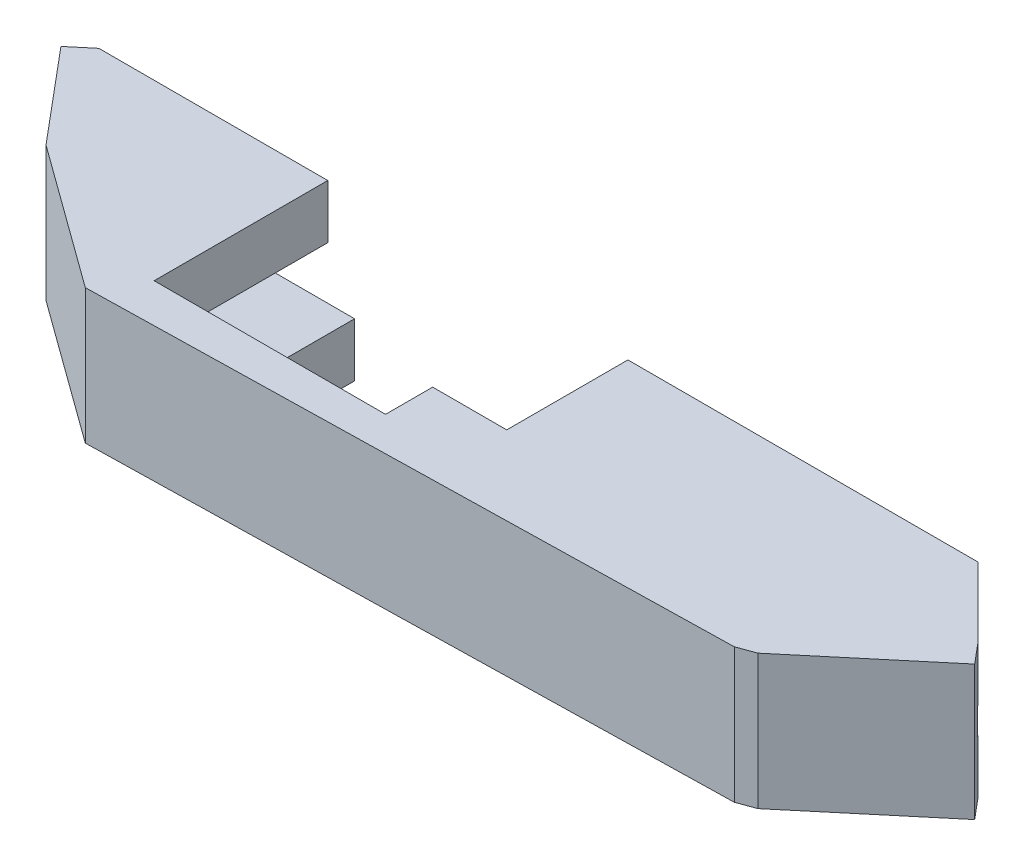
SolidWorks part; units mm, degrees
ref_plane "Front Plane" through (0, 0, 0) normal (0, 0, 1) x (1, 0, 0)
ref_plane "Top Plane" through (0, 0, 0) normal (0, 1, 0) x (1, 0, 0)
ref_plane "Right Plane" through (0, 0, 0) normal (1, 0, 0) x (0, 0, -1)
sketch "Sketch1" plane through (0, 0, 0) normal (0, 1, 0) x (1, 0, 0)
  line L0 (0, 0) -> (28.8, 0)
  line L1 (0, 0) -> (0, 6)
  line L2 (0, 6) -> (-9.1, 6)
  line L3 (0, 6) -> (-2.3, 6)
  line L4 (0, 6) -> (0, 3.7)
  line L5 (39.0587, 0) -> (39.1, 0)
  line L6 (33.95, 4.4993) -> (33.95, 4.1993)
  line L7 (-9.1, 6) -> (-14.8851, 12.8944)
  line L8 (28.8, 0) -> (28.8413, 0)
  line L9 (39.1, 0) -> (47.2, 0)
  line L10 (47.2, 0) -> (55.9543, 7.3457)
  line L11 (33.95, 4.4993) -> (33.95, 5.15)
  line L12 (33.95, 0) -> (33.95, -0.65)
  line L13 (-14.8851, 12.8944) -> (2.1149, 12.8944)
  line L14 (2.1149, 12.8944) -> (2.1149, 0)
  line L15 (28.8, 0) -> (24.8, 0)
  line L16 (24.8, 3.5) -> (24.8, 12.5)
  line L17 (24.8, 12.5) -> (50.8, 12.5)
  line L18 (0, 0) -> (0, -0.3)
  line L19 (50.8, 12.5) -> (55.9543, 7.3457)
  line L20 (24.8, 0) -> (14.8, 0)
  line L21 (14.8, 0) -> (14.8, 3.5)
  line L22 (14.8, 3.5) -> (24.8, 3.5)
  line L23 (0, -0.3) -> (47.2, -0.3)
  line L24 (28.8413, 0) -> (28.8885, 0)
  line L25 (-10.6321, 4.7144) -> (-16.4172, 11.6088)
  line L26 (-14.8851, 12.8944) -> (-16.4172, 11.6088)
  line L27 (0, 0) -> (0, -3)
  line L28 (-10.6321, 4.7144) -> (0, -3)
  line L29 (47.2, 0) -> (47.2, -0.3)
  line L30 (47.2, 0) -> (47.3928, -0.2298)
  line L31 (48.4856, -1.5321) -> (57.2399, 5.8136)
  line L32 (55.9543, 7.3457) -> (57.2399, 5.8136)
  line L33 (47.2, -2) -> (48.4856, -1.5321)
  line L34 (0, -3) -> (47.2, -2)
  line L35 (55.9543, 7.3457) -> (56.1471, 7.1159)
  line L36 (56.1471, 7.1159) -> (47.3092, -0.3)
  line L37 (47.2, -0.3) -> (47.3092, -0.3)
  line L38 (47.4517, -0.3) -> (48.4856, -1.5321)
  line L39 (0, 0) -> (-0.3, 0)
  line L40 (-0.3, 0) -> (-0.3, 4.1175)
  line L41 (-0.3, 0) -> (-0.3, -0.3)
  line L42 (0, -0.3) -> (-0.3, -0.3)
  line L43 (-0.3, 3.7) -> (-2.3, 3.7)
  line L44 (-2.3, 3.7) -> (-2.5121, 3.4879)
  line L45 (-2.3, 3.7) -> (-0.8858, 5.1142)
  line L46 (-2.5121, 3.4879) -> (-0.8858, 5.1142)
  line L47 (28.8413, -0.3) -> (29.0413, -0.3)
  line L48 (-9.1, 5.7) -> (-1.8825, 5.7)
  line L49 (-14.8851, 12.8944) -> (-15.1149, 12.7016)
  line L50 (-15.1149, 12.7016) -> (-9.2399, 5.7)
  line L51 (-9.1, 5.7) -> (-9.2399, 5.7)
  line L52 (29.0413, -0.3) -> (29.0413, 0.6071)
  line L53 (39.0587, -0.3) -> (38.8587, -0.3)
  line L54 (38.8587, -0.3) -> (38.8587, 0.6071)
  arc A0 (0, 3.7) -> (-2.3, 6) centre (-2.3, 3.7) ccw
  arc A1 (39.0587, 0) -> (28.8413, 0) centre (33.95, -0.6507) ccw
  arc A2 (39.0587, -0.3) -> (28.8413, -0.3) centre (33.95, -0.9507) ccw
  arc A3 (-0.3, 4.1175) -> (-1.8825, 5.7) centre (-2.5121, 3.4879) ccw
  dimension "D1" = 28.8
  dimension "D2" = 6
  dimension "D3" = 9.1
  dimension "D4" = 2.3
  dimension "D5" = 2.3
  dimension "D6" = 9
  dimension "D7" = 10.3
  dimension "D8" = 8.1
  dimension "D9" = 130
  dimension "D10" = 140
  dimension "D11" = 5.15
  dimension "D12" = 0.65
  dimension "D13" = 17
  dimension "D14" = 4
  dimension "D15" = 12.5
  dimension "D16" = 26
  dimension "D17" = 0.3
  dimension "D18" = 10
  dimension "D19" = 3.5
  dimension "D20" = 2
  dimension "D21" = 0.2
  dimension "D22" = 3
  dimension "D23" = 2
  dimension "D24" = 90
  dimension "D25" = 2
  dimension "D26" = 2
  dimension "D27" = 0.3
  dimension "D28" = 90
  dimension "D29" = 0.3
  dimension "D30" = 0.3
  dimension "D31" = 45
  dimension "D32" = 0.3
  dimension "D33" = 0.3
  dimension "D34" = 90
  dimension "D35" = 0.2
extrude "Boss-Extrude1" add sketch "Sketch1" along normal blind 4 contours A1 L5 L9 L10 L19 L17 L16 L22 L21 L0 L8 | A2 L6 A1 L24 | L54 A2 L52 L23 | A2 L23 L29 L9 L5 A1 L6 | L23 A2 L54 | L37 L23 L27 L34 L33 L31 L32 L36 | L36 L32 L10 L30 | A2 L24 L8 L0 L18 L23 | L52 A2 L23 | L14 L13 L7 L2 L1 L0 | A3 L40 L39 L1 A0 L2 L7 L26 L50 L51 L48 | L45 A3 L48 L51 L50 L26 L25 L28 L27 L42 L41 L40 L43 | A0 L1 L2 | L40 A3 L45 L43 region at (-4.3342, 0, -8.9115) region at (-0.15, 0, -0.1987) region at (14.4317, 0, 0.15) region at (-0.5137, 0, -5.4863) region at (26.8312, 0, 0.7598) region at (-6.2822, 0, -4.141) region at (37.2188, 0, -6.4157) region at (28.9694, 0, -0.0216) region at (-1.0895, 0, -4.1985) region at (33.95, 0, -1.6) region at (28.8649, 0, -0.0681) region at (38.9306, 0, -0.0216) region at (34.0909, 0, -4.3493) region at (51.6736, 0, -3.558)
extrude "Boss-Extrude2" add sketch "Sketch1<5>" along normal blind 4 contours L42 L18 L39 L41 | L29 L37 L36 L30 region at (-0.15, 0, 0.15) region at (47.2685, 0, 0.1883)
sketch "Sketch1<5>" plane through (0, 0, 0) normal (0, 1, 0) x (1, 0, 0) same geometry as "Sketch1"
extrude "Boss-Extrude3" add sketch "Sketch1<6>" against normal blind 3 contours L37 L23 L27 L34 L33 L31 L32 L36 | L45 A3 L48 L51 L50 L26 L25 L28 L27 L42 L41 L40 L43 | L40 A3 L45 L43 | L54 A2 L52 L23 region at (26.8312, 0, 0.7598) region at (-6.2822, 0, -4.141) region at (-1.0895, 0, -4.1985) region at (33.95, 0, -1.6)
sketch "Sketch1<6>" plane through (0, 0, 0) normal (0, 1, 0) x (1, 0, 0) same geometry as "Sketch1"
ref_plane "Plane1" through (0, -3, 0) normal (0, -1, 0) x (-1, 0, 0)
sketch "Sketch2" plane through (0, -3, 0) normal (0, -1, 0) x (-1, 0, 0)
  line L0 (-47.2, 0) -> (-51.7963, 3.8567)
  line L1 (-51.7963, 3.8567) -> (-51.7963, 10.5333)
  line L2 (-28.8413, 0) -> (-21.2104, 0)
  line L6 (-21.8, 5.0006) -> (-21.8, 11)
  line L7 (-21.8, 11) -> (-51.7963, 11)
  line L11 (-51.7963, 10.5333) -> (-51.7963, 11)
  line L12 (0, 0) -> (-6, 0)
  line L13 (-6, 4.9401) -> (-6, 11)
  line L14 (-6, 11) -> (13.2955, 11)
  line L24 (-21.8, 5.0006) -> (-6, 5.0006)
  line L55 (-21.8, 0) -> (-21.8, -0.3)
  line L56 (-38.8587, -0.3) -> (-38.8587, 0.6071)
  line L57 (-39.0587, -0.3) -> (-38.8587, -0.3)
  line L58 (-29.0413, -0.3) -> (-29.0413, 0.6071)
  line L59 (9.1, 5.7) -> (9.2399, 5.7)
  line L60 (15.1149, 12.7016) -> (9.2399, 5.7)
  line L61 (14.8851, 12.8944) -> (15.1149, 12.7016)
  line L62 (9.1, 5.7) -> (1.8825, 5.7)
  line L63 (-28.8413, -0.3) -> (-29.0413, -0.3)
  line L64 (2.5121, 3.4879) -> (0.8858, 5.1142)
  line L65 (2.3, 3.7) -> (0.8858, 5.1142)
  line L66 (2.3, 3.7) -> (2.5121, 3.4879)
  line L67 (0.3, 3.7) -> (2.3, 3.7)
  line L68 (0, -0.3) -> (0.3, -0.3)
  line L69 (0.3, 0) -> (0.3, -0.3)
  line L70 (0.3, 0) -> (0.3, 4.1175)
  line L71 (0, 0) -> (0.3, 0)
  line L72 (-47.4517, -0.3) -> (-48.4856, -1.5321)
  line L73 (-47.2, -0.3) -> (-47.3092, -0.3)
  line L74 (-56.1471, 7.1159) -> (-47.3092, -0.3)
  line L75 (-55.9543, 7.3457) -> (-56.1471, 7.1159)
  line L76 (0, -3) -> (-47.2, -2)
  line L77 (-47.2, -2) -> (-48.4856, -1.5321)
  line L78 (-55.9543, 7.3457) -> (-57.2399, 5.8136)
  line L79 (-48.4856, -1.5321) -> (-57.2399, 5.8136)
  line L80 (-47.2, 0) -> (-47.3928, -0.2298)
  line L81 (-47.2, 0) -> (-47.2, -0.3)
  line L82 (10.6321, 4.7144) -> (0, -3)
  line L83 (0, 0) -> (0, -3)
  line L84 (14.8851, 12.8944) -> (16.4172, 11.6088)
  line L85 (10.6321, 4.7144) -> (16.4172, 11.6088)
  line L86 (-28.8413, 0) -> (-28.8885, 0)
  line L87 (0, -0.3) -> (-47.2, -0.3)
  line L89 (-14.8, 0) -> (-14.8, 3.5)
  line L90 (-24.8, 0) -> (-14.8, 0)
  line L91 (-50.8, 12.5) -> (-55.9543, 7.3457)
  line L92 (0, 0) -> (0, -0.3)
  line L93 (-24.8, 12.5) -> (-50.8, 12.5)
  line L94 (-24.8, 11) -> (-24.8, 12.5)
  line L95 (-28.8, 0) -> (-24.8, 0)
  line L96 (-2.1149, 12.8944) -> (-2.1149, 0)
  line L97 (14.8851, 12.8944) -> (-2.1149, 12.8944)
  line L98 (-33.95, 0) -> (-33.95, -0.65)
  line L100 (-47.2, 0) -> (-55.9543, 7.3457)
  line L101 (-39.1, 0) -> (-47.2, 0)
  line L102 (-28.8, 0) -> (-28.8413, 0)
  line L103 (9.1, 6) -> (14.8851, 12.8944)
  line L104 (-33.95, 4.4993) -> (-33.95, 4.1993)
  line L105 (-39.0587, 0) -> (-39.1, 0)
  line L106 (0, 6) -> (0, 3.7)
  line L107 (0, 6) -> (2.3, 6)
  line L108 (0, 6) -> (9.1, 6)
  line L109 (0, 0) -> (0, 6)
  line L110 (0, 0) -> (-28.8, 0)
  arc A4 (0.3, 4.1175) -> (1.8825, 5.7) centre (2.5121, 3.4879) cw
  arc A5 (-39.0587, -0.3) -> (-28.8413, -0.3) centre (-33.95, -0.9507) cw
  arc A6 (-39.0587, 0) -> (-28.8413, 0) centre (-33.95, -0.6507) cw
  arc A7 (0, 3.7) -> (2.3, 6) centre (2.3, 3.7) cw
  dimension "D1" = 6
  dimension "D2" = 7
  dimension "D3" = 11
  dimension "D4" = 6
extrude "Boss-Extrude4" add sketch "Sketch2" along normal blind 3.002 and the other way blind 0.998 contours A6 L2 L90 L110 L12 L96 L14 L13 L24 L6 L7 L11 L1 L0 L101 L105 | L83 L87 L63 L57 L73 L74 L78 L79 L77 L76 | L0 L100 L75 L74 L80 | A6 L105 L101 L81 L87 A5 L104 | A5 L57 L56 | A5 L56 L87 L58 | A6 L104 A5 L86 | A5 L58 L63 | L86 A5 L87 L55 L2 | L12 L110 L90 L2 L55 L87 L83 | L12 L109 L106 L107 L108 L103 L14 L96 | A4 L64 L67 L70 L69 L68 L83 L82 L85 L84 L60 L59 L62 | A7 L109 L71 L70 A4 L62 L59 L60 L61 L103 L108 | A4 L70 L67 L64 | L106 A7 L107 | L71 L83 L68 L69 | L81 L80 L74 L73 region at (51.6736, -3, -3.558) region at (47.2685, -3, 0.1883) region at (43.15, -3, 0.1409) region at (28.8835, -3, -5.32) region at (26.8312, -3, 0.7598) region at (38.9306, -3, -0.0216) region at (33.95, -3, -1.6) region at (30.5912, -3, -3.163) region at (25.3317, -3, 0.1498) region at (28.9694, -3, -0.0216) region at (-6.2822, -3, -4.141) region at (-0.15, -3, 0.15) region at (10.9, -3, 0.15) region at (-0.1987, -3, -1.85) region at (-3.6912, -3, -7.7297) region at (-0.5137, -3, -5.4863) region at (-1.0895, -3, -4.1985)
ref_plane "Plane2" through (0, 4, 0) normal (0, 1, 0) x (1, 0, 0)
sketch "Sketch3" plane through (0, 4, 0) normal (0, 1, 0) x (1, 0, 0)
  line L0 (14.8, 0) -> (19.3, 0)
  line L1 (14.8, 0) -> (14.8, 3.5)
  line L2 (19.3, 0) -> (19.3, 3.5)
  line L3 (14.8, 3.5) -> (24.8, 3.5) construction
  line L4 (19.3, 3.5) -> (14.8, 3.5)
  dimension "D1" = 4.5
extrude "Cut-Extrude1" cut sketch "Sketch3" against normal blind 4
